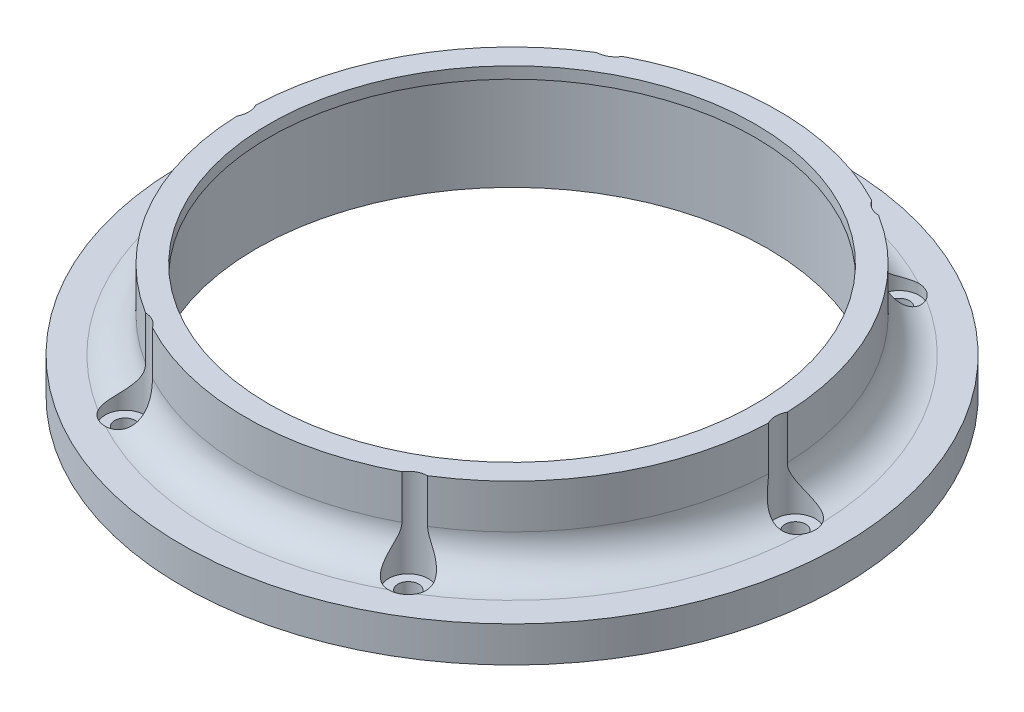
SolidWorks part; units mm, degrees
ref_plane "Front Plane" through (0, 0, 0) normal (0, 0, 1) x (1, 0, 0)
ref_plane "Top Plane" through (0, 0, 0) normal (0, 1, 0) x (1, 0, 0)
ref_plane "Right Plane" through (0, 0, 0) normal (1, 0, 0) x (0, 0, -1)
sketch "Sketch1" plane through (0, 0, 0) normal (0, 1, 0) x (1, 0, 0)
  circle A0 centre (0, 0) radius 61.25 construction
  circle A1 centre (0, 0) radius 55.25
  circle A2 centre (0, 0) radius 57.5
  dimension "D1" = 122.5
  dimension "D2" = 110.5
  dimension "D3" = 115
extrude "Boss-Extrude1" add sketch "Sketch1" along normal blind 22
sketch "Sketch2" plane through (0, 0, 0) normal (0, -1, 0) x (1, 0, 0)
  circle A0 centre (0, 0) radius 61.25 construction
  circle A1 centre (0, 0) radius 71.25
  circle A2 centre (0, 0) radius 57.5 construction
  circle A3 centre (0, 0) radius 57.5
  dimension "D1" = 122.5
  dimension "D2" = 10
extrude "Boss-Extrude2" add sketch "Sketch2" against normal blind 7.5
hole_wizard "CBORE for M4 SBHCS1" positions "Sketch6" profile "Sketch5" counterbore size "M4" standard "ANSI Metric" end condition through all
sketch "Sketch6" plane through (0, 7.5, 0) normal (0, 1, 0) x (1, 0, 0)
  circle A0 centre (0, 0) radius 61.25 construction
  point P0 (-61.25, 0)
  dimension "D1" = 122.5
sketch "Sketch5" plane through (-61.25, 7.5, 0) normal (1, 0, 0) x (0, 0, 1)
  line L0 (0, 0) -> (0, 7.5)
  line L1 (0, 7.5) -> (2.25, 7.5)
  line L3 (2.25, 7.5) -> (2.25, 2.2)
  line L4 (2.25, 2.2) -> (4.3, 2.2)
  line L5 (4.3, 2.2) -> (4.3, 0)
  line L7 (4.3, 0) -> (0, 0)
  line L11 (0, -6.35) -> (0, 107.95) construction
  dimension "Thru Hole Dia." = 4.5
  dimension "Thru Hole Depth" = 7.5
  dimension "C'Bore Dia." = 8.6
  dimension "C'Bore Depth" = 2.2
fillet "Fillet2" radius 7.5 1 edges at (57.5, 7.5, 0)
sketch "Sketch7" plane through (0, 7.5, 0) normal (0, 1, 0) x (1, 0, 0)
  circle A1 centre (-61.25, 0) radius 4.3
  circle A2 centre (-61.25, 0) radius 4.3
  dimension "D1" = 0
extrude "Cut-Extrude1" cut sketch "Sketch7" along normal through all
pattern_circular "CirPattern1" count 6 over 360 about axis through (0, 7.5, 0) along (0, -1, 0) of "Cut-Extrude1", "CBORE for M4 SBHCS1"
sketch "Sketch8" plane through (0, 22, 0) normal (0, 1, 0) x (1, 0, 0)
  circle A0 centre (0, 0) radius 52.5
  arc A12 (-57.4639, -2.0384) -> (-30.4972, -48.746) centre (0, 0) ccw
  arc A13 (-26.9666, -50.7844) -> (-30.4972, -48.746) centre (-30.625, -53.0441) ccw
  arc A14 (-26.9666, -50.7844) -> (26.9666, -50.7844) centre (0, 0) ccw
  arc A15 (30.4972, -48.746) -> (26.9666, -50.7844) centre (30.625, -53.0441) ccw
  arc A16 (30.4972, -48.746) -> (57.4639, -2.0384) centre (0, 0) ccw
  arc A17 (57.4639, 2.0384) -> (57.4639, -2.0384) centre (61.25, 0) ccw
  arc A18 (57.4639, 2.0384) -> (30.4972, 48.746) centre (0, 0) ccw
  arc A19 (26.9666, 50.7844) -> (30.4972, 48.746) centre (30.625, 53.0441) ccw
  arc A20 (26.9666, 50.7844) -> (-26.9666, 50.7844) centre (0, 0) ccw
  arc A21 (-30.4972, 48.746) -> (-26.9666, 50.7844) centre (-30.625, 53.0441) ccw
  arc A22 (-30.4972, 48.746) -> (-57.4639, 2.0384) centre (0, 0) ccw
  arc A23 (-57.4639, -2.0384) -> (-57.4639, 2.0384) centre (-61.25, 0) ccw
  arc A24 (-57.4639, -2.0384) -> (-30.4972, -48.746) centre (0, 0) ccw
  arc A25 (-26.9666, -50.7844) -> (-30.4972, -48.746) centre (-30.625, -53.0441) ccw
  arc A26 (-26.9666, -50.7844) -> (26.9666, -50.7844) centre (0, 0) ccw
  arc A27 (30.4972, -48.746) -> (26.9666, -50.7844) centre (30.625, -53.0441) ccw
  arc A28 (30.4972, -48.746) -> (57.4639, -2.0384) centre (0, 0) ccw
  arc A29 (57.4639, 2.0384) -> (57.4639, -2.0384) centre (61.25, 0) ccw
  arc A30 (57.4639, 2.0384) -> (30.4972, 48.746) centre (0, 0) ccw
  arc A31 (26.9666, 50.7844) -> (30.4972, 48.746) centre (30.625, 53.0441) ccw
  arc A32 (26.9666, 50.7844) -> (-26.9666, 50.7844) centre (0, 0) ccw
  arc A33 (-30.4972, 48.746) -> (-26.9666, 50.7844) centre (-30.625, 53.0441) ccw
  arc A34 (-30.4972, 48.746) -> (-57.4639, 2.0384) centre (0, 0) ccw
  arc A35 (-57.4639, -2.0384) -> (-57.4639, 2.0384) centre (-61.25, 0) ccw
  dimension "D2" = 5
  dimension "D1" = 0
extrude "Boss-Extrude3" add sketch "Sketch8" along normal blind 2.5
sketch "Sketch10" plane through (0, 0, 0) normal (0, -1, 0) x (1, 0, 0)
  circle A0 centre (0, 0) radius 55.25 construction
  circle A1 centre (0, 0) radius 71.25
  circle A2 centre (0, 0) radius 71.25
  circle A3 centre (61.25, 0) radius 2.25 construction
  circle A4 centre (30.625, 53.0441) radius 2.25 construction
  circle A5 centre (-30.625, 53.0441) radius 2.25 construction
  circle A6 centre (-61.25, 0) radius 2.25 construction
  circle A7 centre (-30.625, -53.0441) radius 2.25 construction
  circle A8 centre (30.625, -53.0441) radius 2.25 construction
  circle A9 centre (0, 0) radius 55.25
  circle A10 centre (61.25, 0) radius 2.25
  circle A11 centre (30.625, 53.0441) radius 2.25
  circle A12 centre (-30.625, 53.0441) radius 2.25
  circle A13 centre (-61.25, 0) radius 2.25
  circle A14 centre (-30.625, -53.0441) radius 2.25
  circle A15 centre (30.625, -53.0441) radius 2.25
  dimension "D1" = 0
extrude "Boss-Extrude4" add sketch "Sketch10" along normal blind 0.2
